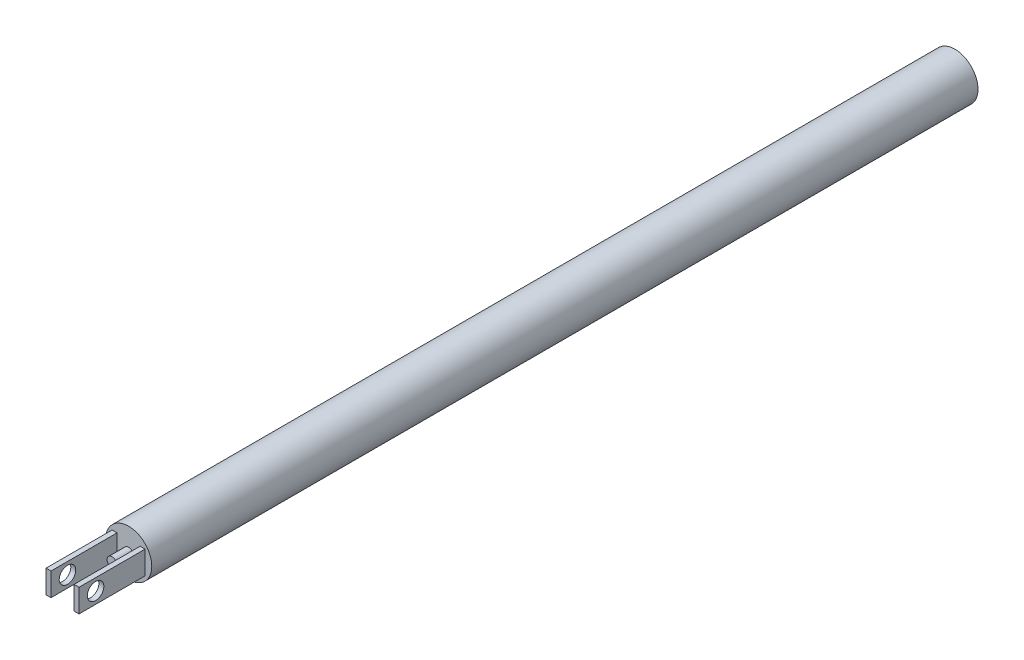
SolidWorks part; units mm, degrees
ref_plane "Front Plane" through (0, 0, 0) normal (0, 0, 1) x (1, 0, 0)
ref_plane "Top Plane" through (0, 0, 0) normal (0, 1, 0) x (1, 0, 0)
ref_plane "Right Plane" through (0, 0, 0) normal (1, 0, 0) x (0, 0, -1)
sketch "Sketch1" plane through (0, 0, 0) normal (0, 0, 1) x (1, 0, 0)
  circle A0 centre (0, 0) radius 7
  dimension "D1" = 14
extrude "Boss-Extrude1" add sketch "Sketch1" along normal blind 125 and the other way blind 125
sketch "Sketch2" plane through (0, 0, 0) normal (1, 0, 0) x (0, 0, -1)
  line L0 (-145, -3.5) -> (-125, -3.5)
  line L1 (-145, -3.5) -> (-145, 3.5)
  line L2 (-125, -3.5) -> (-125, 3.5)
  line L3 (-145, 3.5) -> (-125, 3.5)
  line L4 (-125, 0) -> (-145, 0) construction
  line L5 (-135, -3.5) -> (-135, 3.5) construction
  line L6 (-125, 7) -> (-125, -7) construction
  line L7 (-8.1311, 0) -> (-128.7394, 0) construction
  circle A0 centre (-140, 0) radius 2.5
  point P1 (-135, 0)
  point P9 (0, 0)
  point P10 (-128.7394, 0)
  dimension "D3" = 5
  dimension "D4" = 5
  dimension "D1" = 20
  dimension "D2" = 7
extrude "Boss-Extrude2" add sketch "Sketch2" along normal blind 5 and the other way blind 5
sketch "Sketch4" plane through (0, 0, 145) normal (0, 0, 1) x (1, 0, 0)
  line L0 (-5, 3.5) -> (5, 3.5) construction
  line L1 (-3.5, -3.5) -> (3.5, -3.5)
  line L2 (-3.5, -3.5) -> (-3.5, 3.5)
  line L3 (-3.5, 3.5) -> (3.5, 3.5)
  line L4 (3.5, -3.5) -> (3.5, 3.5)
  line L5 (0, 3.5) -> (0, -3.5) construction
  line L6 (-3.5, 0) -> (3.5, 0) construction
  point P0 (0, 0)
  dimension "D1" = 7
extrude "Cut-Extrude1" cut sketch "Sketch4" against normal up to surface (20 mm away) up to face at (7, 0, 125)
sketch "Sketch5" plane through (0, 0, 125) normal (0, 0, 1) x (1, 0, 0)
  circle A0 centre (0, 0) radius 1.5
  dimension "D1" = 3
extrude "Boss-Extrude3" add sketch "Sketch5" along normal blind 5
